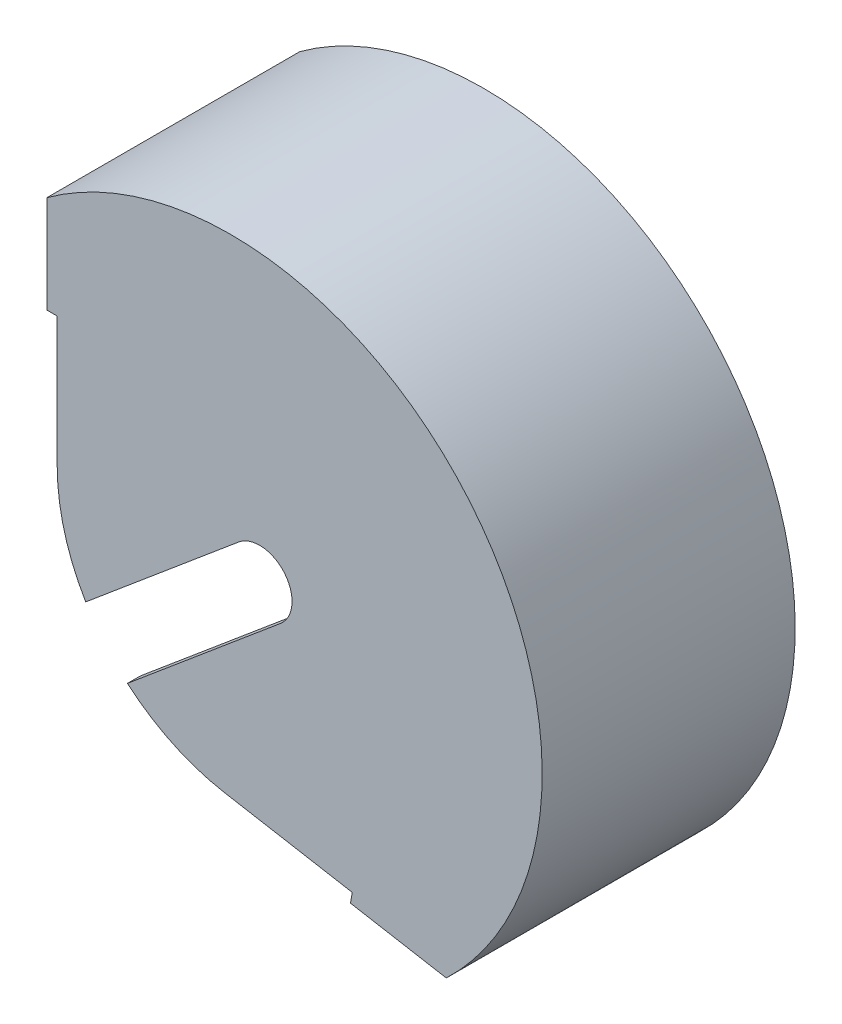
SolidWorks part; units mm, degrees
ref_plane "Front Plane" through (0, 0, 0) normal (0, 0, 1) x (1, 0, 0)
ref_plane "Top Plane" through (0, 0, 0) normal (0, 1, 0) x (1, 0, 0)
ref_plane "Right Plane" through (0, 0, 0) normal (1, 0, 0) x (0, 0, -1)
sketch "Sketch1" plane through (0, 0, 0) normal (0, 0, 1) x (1, 0, 0)
  line L0 (0, 0) -> (-39.624, 0)
  line L1 (0, 0) -> (-6.8806, -39.022)
  line L2 (-39.624, 0) -> (-39.624, 25.4)
  line L3 (-6.8806, -39.022) -> (18.1335, -43.4327)
  line L4 (-39.624, 25.4) -> (-41.656, 25.4)
  line L5 (18.1335, -43.4327) -> (17.7806, -45.4338)
  line L6 (-41.656, 25.4) -> (-41.656, 44.45)
  line L7 (17.7806, -45.4338) -> (36.5412, -48.7418)
  arc A0 (-39.624, 0) -> (-6.8806, -39.022) centre (0, 0) ccw
  arc A1 (36.5412, -48.7418) -> (-41.656, 44.45) centre (-5.6446, -4.7364) ccw
  dimension "D1" = 79.248
  dimension "D8" = 60.96
  dimension "D2" = 80
  dimension "D3" = 25.4
  dimension "D4" = 25.4
  dimension "D5" = 2.032
  dimension "D6" = 2.032
  dimension "D7" = 19.05
extrude "Side" add sketch "Sketch1" along normal blind 2.54 contours L7 A1 L6 L4 L2 L0 L1 L3 L5 | L0 A0 L1 region at (-18.6316, -15.6338, 0) region at (10.1938, 8.5536, 0)
sketch "Sketch2" plane through (0, 0, 2.54) normal (0, 0, 1) x (1, 0, 0)
  line L0 (-40.1555, 42.4006) -> (-41.656, 42.4006)
  line L2 (34.7835, -46.9083) -> (34.5229, -48.3859)
  line L4 (-41.656, 25.4) -> (-41.656, 44.45) construction
  line L5 (17.7806, -45.4338) -> (36.5412, -48.7418) construction
  line L6 (-41.656, 42.4006) -> (-41.656, 44.45)
  line L7 (34.5229, -48.3859) -> (36.5412, -48.7418)
  arc A2 (34.7835, -46.9083) -> (-40.1555, 42.4006) centre (-5.6446, -4.7364) ccw
  arc A3 (34.7835, -46.9083) -> (-40.1555, 42.4006) centre (-5.6446, -4.7364) ccw
  arc A5 (36.5412, -48.7418) -> (-41.656, 44.45) centre (-5.6446, -4.7364) ccw
  arc A6 (36.5412, -48.7418) -> (-41.656, 44.45) centre (-5.6446, -4.7364) ccw
  line M6 (18.1335, -43.4327) -> (17.7806, -45.4338)
  line M7 (17.7806, -45.4338) -> (36.5412, -48.7418)
  arc M8 (36.5412, -48.7418) -> (-41.656, 44.45) centre (-5.6446, -4.7364) ccw
  line M9 (-41.656, 44.45) -> (-41.656, 25.4)
  line M10 (-41.656, 25.4) -> (-39.624, 25.4)
  dimension "D1" = 2.54
  dimension "D2" = 0
extrude "Cover" add sketch "Sketch2" along normal blind 44.45 contours A3 L2 L0 M6 M7 M8 M9 M10 region at (-40.9058, 43.8296, 2.54)
ref_plane "midplane" through (0, 0, 24.765) normal (0, 0, 1) x (1, 0, 0)
mirror "Mirror1" about plane through (0, 0, 24.765) normal (0, 0, 1) of "Side"
sketch "Sketch3" plane through (0, 0, 49.53) normal (0, 0, 1) x (1, 0, 0)
  line L0 (0, 0) -> (-30.3537, -25.4698) construction
  line L1 (-4.0817, 4.8644) -> (-37.1595, -22.8912)
  line L2 (-37.1595, -22.8912) -> (-28.9961, -32.62)
  line L3 (-28.9961, -32.62) -> (4.0817, -4.8644)
  arc A0 (4.0817, -4.8644) -> (-4.0817, 4.8644) centre (0, 0) ccw
  arc A1 (-39.624, 0) -> (-6.8806, -39.022) centre (0, 0) ccw construction
  dimension "D2" = 12.7
  dimension "D1" = 43.18
extrude "Flywheel slit" cut sketch "Sketch3" against normal up to next
sketch "Sketch4" plane through (0, 0, 0) normal (0, 0, -1) x (-1, 0, 0)
  line L0 (0, 0) -> (39.624, 0) construction
  line L1 (0, 0) -> (33.2775, 10.174) construction
  line L2 (-2.1162, -33.5317) -> (33.2775, 10.174) construction
  line L3 (33.2775, 10.174) -> (3.2382, -36.9452) construction
  line L4 (3.2382, -36.9452) -> (-2.1162, -33.5317) construction
  circle A2 centre (-2.1162, -33.5317) radius 3.2639
  circle A3 centre (33.2775, 10.174) radius 3.2639
  dimension "D1" = 6.35
  dimension "D2" = 55.88
  dimension "D4" = 6.5278
  dimension "D5" = 17
extrude "Mount holes" cut sketch "Sketch4" against normal up to next
